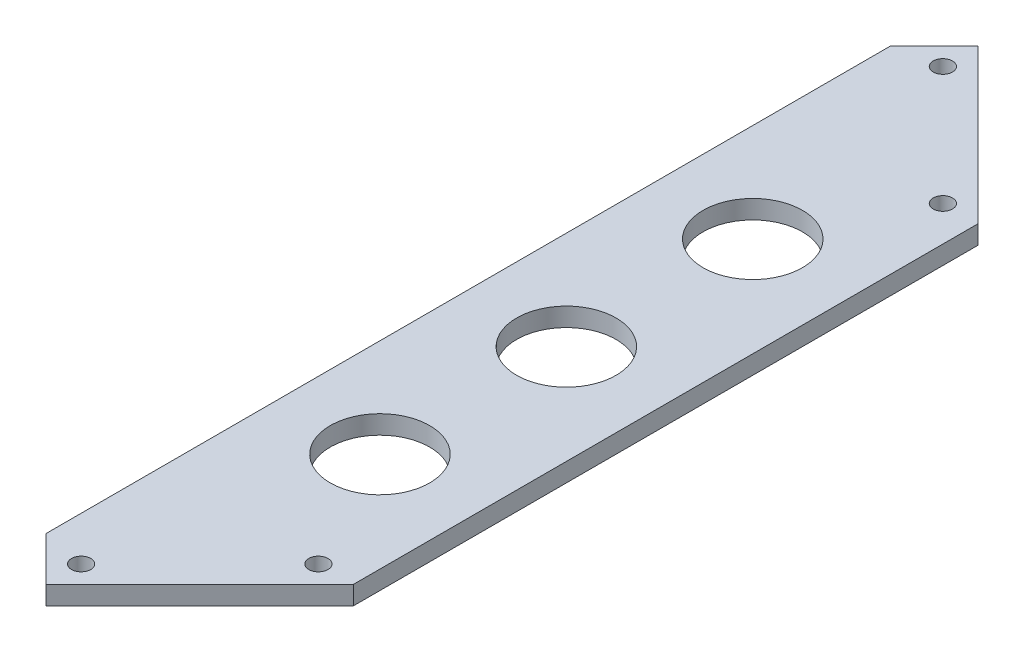
SolidWorks part; units mm, degrees
ref_plane "Front Plane" through (0, 0, 0) normal (0, 0, 1) x (1, 0, 0)
ref_plane "Top Plane" through (0, 0, 0) normal (0, 1, 0) x (1, 0, 0)
ref_plane "Right Plane" through (0, 0, 0) normal (1, 0, 0) x (0, 0, -1)
sketch "Sketch1" plane through (0, 0, 0) normal (0, 1, 0) x (1, 0, 0)
  line L1 (-75, 75) -> (75, 75)
  line L2 (-75, 75) -> (-75, -75)
  line L3 (-75, -75) -> (75, -75)
  line L4 (75, 75) -> (75, -75)
  line L5 (-75, 75) -> (75, -75) construction
  line L6 (-75, -75) -> (75, 75) construction
  point P0 (0, 0)
  dimension "D1" = 150
extrude "Boss-Extrude1" add sketch "Sketch1" along normal mid plane 3
sketch "Sketch2" plane through (0, 1.5, 0) normal (0, 1, 0) x (1, 0, 0)
  line L0 (50.2513, 75) -> (75, 75)
  line L1 (-15, 15) -> (15, 15)
  line L2 (-15, 15) -> (-15, -15)
  line L3 (-15, -15) -> (15, -15)
  line L4 (15, 15) -> (15, -15)
  line L5 (-15, 15) -> (15, -15) construction
  line L6 (-15, -15) -> (15, 15) construction
  line L7 (75, 75) -> (-75, 75) construction
  line L8 (75, -75) -> (75, 75) construction
  line L9 (75, 75) -> (75, 50.2513)
  line L10 (75, 50.2513) -> (50.2513, 75)
  line L11 (0, 0) -> (-24.6603, 0) construction
  line L12 (0, 0) -> (0, -37.7235) construction
  line L13 (-75, 75) -> (-75, 50.2513)
  line L14 (-50.2513, 75) -> (-75, 75)
  line L15 (-75, 50.2513) -> (-50.2513, 75)
  line L16 (-50.2513, -75) -> (-75, -75)
  line L17 (-75, -50.2513) -> (-50.2513, -75)
  line L18 (-75, -75) -> (-75, -50.2513)
  line L19 (75, -75) -> (75, -50.2513)
  line L20 (50.2513, -75) -> (75, -75)
  line L21 (75, -50.2513) -> (50.2513, -75)
  point P0 (0, 0)
  dimension "D1" = 30
  dimension "D2" = 35
extrude "Cut-Extrude1" cut sketch "Sketch2" against normal up to surface (3 mm away) contours L10 L0 L9 | L13 L15 L14 | L19 L21 L20 | L16 L18 L17 up to face at (0, -1.5, 0)
sketch "Sketch3" plane through (0, 1.5, 0) normal (0, 1, 0) x (1, 0, 0)
  line L0 (75, 50.2513) -> (50.2513, 75) construction
  line L1 (10, 10) -> (-10, 10)
  line L2 (10, 10) -> (10, -10)
  line L3 (10, -10) -> (-10, -10)
  line L4 (-10, 10) -> (-10, -10)
  line L5 (10, 10) -> (-10, -10) construction
  line L6 (10, -10) -> (-10, 10) construction
  line L7 (0, 0) -> (0, -7.7356) construction
  line L8 (0, 0) -> (-6.2026, 0) construction
  circle A2 centre (69.3431, 50.2513) radius 1.55
  circle A6 centre (50.2513, 69.3431) radius 1.55
  circle A7 centre (-69.3431, 50.2513) radius 1.55
  circle A12 centre (-50.2513, 69.3431) radius 1.55
  circle A14 centre (-69.3431, -50.2513) radius 1.55
  circle A18 centre (-50.2513, -69.3431) radius 1.55
  circle A19 centre (69.3431, -50.2513) radius 1.55
  circle A24 centre (50.2513, -69.3431) radius 1.55
  point P0 (0, 0)
  dimension "D2" = 13.5
  dimension "D4" = 3.1
  dimension "D8" = 4
  dimension "D1" = 20
extrude "Cut-Extrude2" cut sketch "Sketch3" against normal up to surface (3 mm away) contours A12 | A7 | A14 | A18 | A19 | A24 | A2 | A6 region at (69.3431, 1.5, -50.2513) region at (50.2513, 1.5, -69.3431) region at (-69.3431, 1.5, -50.2513) region at (-50.2513, 1.5, -69.3431) region at (-69.3431, 1.5, 50.2513) region at (-50.2513, 1.5, 69.3431) region at (69.3431, 1.5, 50.2513) region at (50.2513, 1.5, 69.3431) up to face at (0, -1.5, 0)
sketch "Sketch4" plane through (0, 1.5, 0) normal (0, 1, 0) x (1, 0, 0)
  line L1 (50.2513, 75) -> (-50.2513, 75)
  line L2 (-50.2513, 75) -> (-75, 50.2513)
  line L3 (-75, 50.2513) -> (-75, -50.2513)
  line L4 (-75, -50.2513) -> (-50.2513, -75)
  line L5 (-50.2513, -75) -> (50.2513, -75)
  line L7 (50.2513, 75) -> (43.1802, 67.9289)
  line L8 (43.1802, 67.9289) -> (43.1802, -67.9289)
  line L9 (43.1802, -67.9289) -> (50.2513, -75)
  line L10 (75, 50.2513) -> (50.2513, 75) construction
  line L11 (75, -50.2513) -> (50.2513, -75) construction
  dimension "D1" = 10
extrude "Cut-Extrude3" cut sketch "Sketch4" against normal up to surface (3 mm away) up to face at (-69.3431, -1.5, 51.8013)
sketch "Sketch5" plane through (0, 1.5, 0) normal (0, 1, 0) x (1, 0, 0)
  line L0 (75, -50.2513) -> (75, 50.2513) construction
  line L1 (0, 0) -> (-10.9556, 0) construction
  circle A0 centre (59, 0) radius 8
  circle A1 centre (59, 30) radius 8
  circle A4 centre (59, -30) radius 8
  dimension "D1" = 16
  dimension "D2" = 16
  dimension "D3" = 30
extrude "Cut-Extrude4" cut sketch "Sketch5" against normal up to surface (3 mm away) up to face at (56.1438, -1.5, 0)
